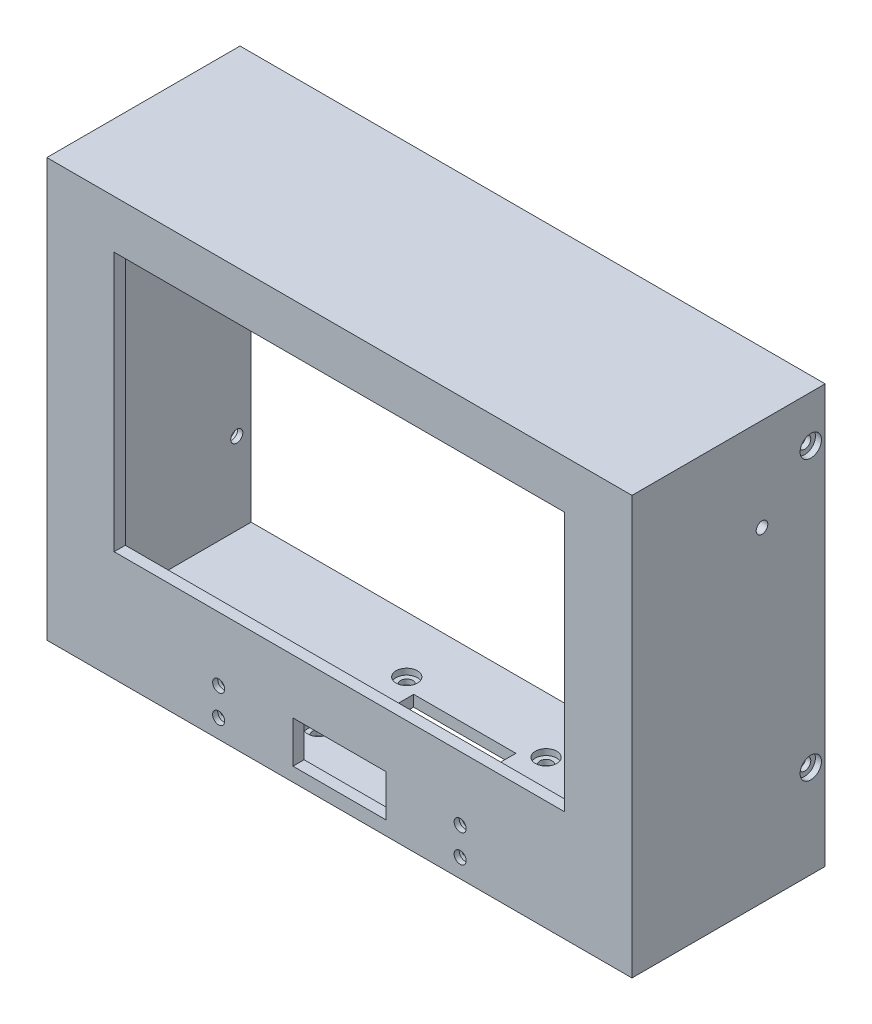
SolidWorks part; units mm, degrees
ref_plane "Front Plane" through (0, 0, 0) normal (0, 0, 1) x (1, 0, 0)
ref_plane "Top Plane" through (0, 0, 0) normal (0, 1, 0) x (1, 0, 0)
ref_plane "Right Plane" through (0, 0, 0) normal (1, 0, 0) x (0, 0, -1)
sketch "Sketch1" plane through (0, 0, 0) normal (0, 0, 1) x (1, 0, 0)
  line L1 (-63, 60) -> (63, 60)
  line L2 (-63, 60) -> (-63, 150)
  line L3 (-63, 150) -> (63, 150)
  line L4 (63, 60) -> (63, 150)
extrude "Boss-Extrude1" add sketch "Sketch1" along normal blind 41.6 from offset 38.4
sketch "Sketch2" plane through (0, 0, 0) normal (0, 0, 1) x (1, 0, 0)
  line L1 (-60.6, 62.4) -> (60.6, 62.4)
  line L2 (-60.6, 62.4) -> (-60.6, 147.6)
  line L3 (-60.6, 147.6) -> (60.6, 147.6)
  line L4 (60.6, 62.4) -> (60.6, 147.6)
extrude "Boss-Extrude2" add sketch "Sketch2" along normal blind 41.6 from offset 36 separate body
combine bodies "Combine1" operation type subtract main body 101 bodies to subtract 102
sketch "Sketch3" plane through (0, 0, 0) normal (0, 0, 1) x (1, 0, 0)
  line L1 (-48.5, 83.74) -> (48.5, 83.74)
  line L2 (-48.5, 83.74) -> (-48.5, 139.6)
  line L3 (-48.5, 139.6) -> (48.5, 139.6)
  line L4 (48.5, 83.74) -> (48.5, 139.6)
extrude "Boss-Extrude3" add sketch "Sketch3" along normal blind 4.4 from offset 76.6 separate body
combine bodies "Combine2" operation type subtract main body 103 bodies to subtract 104
sketch "Sketch4" plane through (0, 0, 0) normal (0, 0, 1) x (1, 0, 0)
  circle A0 centre (-56.3, 78.45) radius 2.8
extrude "Boss-Extrude4" add sketch "Sketch4" along normal blind 4.5 from offset 73.1
sketch "Sketch5" plane through (0, 0, 0) normal (0, 0, 1) x (1, 0, 0)
  circle A0 centre (-56.3, 78.45) radius 1
extrude "Boss-Extrude5" add sketch "Sketch5" along normal blind 7.1 from offset 72.1 separate body
combine bodies "Combine3" operation type subtract main body 106 bodies to subtract 107
sketch "Sketch6" plane through (0, 0, 0) normal (0, 0, 1) x (1, 0, 0)
  circle A0 centre (-56.3, 140.55) radius 2.8
extrude "Boss-Extrude6" add sketch "Sketch6" along normal blind 4.5 from offset 73.1
sketch "Sketch7" plane through (0, 0, 0) normal (0, 0, 1) x (1, 0, 0)
  circle A0 centre (-56.3, 140.55) radius 1
extrude "Boss-Extrude7" add sketch "Sketch7" along normal blind 7.1 from offset 72.1 separate body
combine bodies "Combine4" operation type subtract main body 109 bodies to subtract 110
sketch "Sketch8" plane through (0, 0, 0) normal (0, 0, 1) x (1, 0, 0)
  circle A0 centre (56.3, 78.45) radius 2.8
extrude "Boss-Extrude8" add sketch "Sketch8" along normal blind 4.5 from offset 73.1
sketch "Sketch9" plane through (0, 0, 0) normal (0, 0, 1) x (1, 0, 0)
  circle A0 centre (56.3, 78.45) radius 1
extrude "Boss-Extrude9" add sketch "Sketch9" along normal blind 7.1 from offset 72.1 separate body
combine bodies "Combine5" operation type subtract main body 112 bodies to subtract 113
sketch "Sketch10" plane through (0, 0, 0) normal (0, 0, 1) x (1, 0, 0)
  circle A0 centre (56.3, 140.55) radius 2.8
extrude "Boss-Extrude10" add sketch "Sketch10" along normal blind 4.5 from offset 73.1
sketch "Sketch11" plane through (0, 0, 0) normal (0, 0, 1) x (1, 0, 0)
  circle A0 centre (56.3, 140.55) radius 1
extrude "Boss-Extrude11" add sketch "Sketch11" along normal blind 7.1 from offset 72.1 separate body
combine bodies "Combine6" operation type subtract main body 115 bodies to subtract 116
sketch "Sketch12" plane through (0, 0, 0) normal (0, 0, 1) x (1, 0, 0)
  line L1 (-64, 107.5) -> (-60.1, 107.5)
  line L2 (-64, 107.5) -> (-64, 121.5)
  line L3 (-64, 121.5) -> (-60.1, 121.5)
  line L4 (-60.1, 107.5) -> (-60.1, 121.5)
extrude "Boss-Extrude12" add sketch "Sketch12" along normal blind 8 from offset 65.9 separate body
combine bodies "Combine7" operation type subtract main body 117 bodies to subtract 118
sketch "Sketch13" plane through (0, 0, 0) normal (1, 0, 0) x (0, 0, -1)
  circle A0 centre (-52, 130) radius 8.3
extrude "Boss-Extrude13" add sketch "Sketch13" along normal blind 1.2 from offset 60.6 offset against normal yes
sketch "Sketch14" plane through (0, 0, 0) normal (1, 0, 0) x (0, 0, -1)
  circle A0 centre (-52, 130) radius 7.3
extrude "Boss-Extrude14" add sketch "Sketch14" along normal blind 1.3 from offset 60.6 separate body offset against normal yes
combine bodies "Combine8" operation type subtract main body 120 bodies to subtract 121
sketch "Sketch15" plane through (0, 0, 0) normal (1, 0, 0) x (0, 0, -1)
  circle A0 centre (-52, 130) radius 1.25
extrude "Boss-Extrude15" add sketch "Sketch15" along normal blind 4.4 from offset 64 separate body offset against normal yes
combine bodies "Combine9" operation type subtract main body 122 bodies to subtract 123
sketch "Sketch16" plane through (0, 0, 0) normal (1, 0, 0) x (0, 0, -1)
  circle A0 centre (-41.5, 80) radius 1.3
extrude "Boss-Extrude16" add sketch "Sketch16" along normal blind 4.4 from offset 64 separate body offset against normal yes
combine bodies "Combine10" operation type subtract main body 124 bodies to subtract 125
sketch "Sketch17" plane through (0, 0, 0) normal (1, 0, 0) x (0, 0, -1)
  circle A0 centre (-41.5, 80) radius 2.3
extrude "Boss-Extrude17" add sketch "Sketch17" along normal blind 2.3 from offset 64 separate body offset against normal yes
combine bodies "Combine11" operation type subtract main body 126 bodies to subtract 127
sketch "Sketch18" plane through (0, 0, 0) normal (1, 0, 0) x (0, 0, -1)
  circle A0 centre (-41.5, 140) radius 1.3
extrude "Boss-Extrude18" add sketch "Sketch18" along normal blind 4.4 from offset 64 separate body offset against normal yes
combine bodies "Combine12" operation type subtract main body 128 bodies to subtract 129
sketch "Sketch19" plane through (0, 0, 0) normal (1, 0, 0) x (0, 0, -1)
  circle A0 centre (-41.5, 140) radius 2.3
extrude "Boss-Extrude19" add sketch "Sketch19" along normal blind 2.3 from offset 64 separate body offset against normal yes
combine bodies "Combine13" operation type subtract main body 130 bodies to subtract 131
sketch "Sketch20" plane through (0, 0, 0) normal (1, 0, 0) x (0, 0, -1)
  circle A0 centre (-52, 130) radius 8.3
extrude "Boss-Extrude20" add sketch "Sketch20" along normal blind 1.2 from offset 59.4
sketch "Sketch21" plane through (0, 0, 0) normal (1, 0, 0) x (0, 0, -1)
  circle A0 centre (-52, 130) radius 7.3
extrude "Boss-Extrude21" add sketch "Sketch21" along normal blind 1.3 from offset 59.3 separate body
combine bodies "Combine14" operation type subtract main body 133 bodies to subtract 134
sketch "Sketch22" plane through (0, 0, 0) normal (1, 0, 0) x (0, 0, -1)
  circle A0 centre (-52, 130) radius 1.25
extrude "Boss-Extrude22" add sketch "Sketch22" along normal blind 4.4 from offset 59.6 separate body
combine bodies "Combine15" operation type subtract main body 135 bodies to subtract 136
sketch "Sketch23" plane through (0, 0, 0) normal (1, 0, 0) x (0, 0, -1)
  circle A0 centre (-41.5, 80) radius 1.3
extrude "Boss-Extrude23" add sketch "Sketch23" along normal blind 4.4 from offset 59.6 separate body
combine bodies "Combine16" operation type subtract main body 137 bodies to subtract 138
sketch "Sketch24" plane through (0, 0, 0) normal (1, 0, 0) x (0, 0, -1)
  circle A0 centre (-41.5, 80) radius 2.3
extrude "Boss-Extrude24" add sketch "Sketch24" along normal blind 2.3 from offset 61.7 separate body
combine bodies "Combine17" operation type subtract main body 139 bodies to subtract 140
sketch "Sketch25" plane through (0, 0, 0) normal (1, 0, 0) x (0, 0, -1)
  circle A0 centre (-41.5, 140) radius 1.3
extrude "Boss-Extrude25" add sketch "Sketch25" along normal blind 4.4 from offset 59.6 separate body
combine bodies "Combine18" operation type subtract main body 141 bodies to subtract 142
sketch "Sketch26" plane through (0, 0, 0) normal (1, 0, 0) x (0, 0, -1)
  circle A0 centre (-41.5, 140) radius 2.3
extrude "Boss-Extrude26" add sketch "Sketch26" along normal blind 2.3 from offset 61.7 separate body
combine bodies "Combine19" operation type subtract main body 143 bodies to subtract 144
sketch "Sketch27" plane through (0, 0, 0) normal (0, 0, 1) x (1, 0, 0)
  line L1 (-11, 59) -> (11, 59)
  line L2 (-11, 59) -> (-11, 63.4)
  line L3 (-11, 63.4) -> (11, 63.4)
  line L4 (11, 59) -> (11, 63.4)
extrude "Boss-Extrude27" add sketch "Sketch27" along normal blind 14 from offset 53 separate body
combine bodies "Combine20" operation type subtract main body 145 bodies to subtract 146
sketch "Sketch28" plane through (0, 0, 0) normal (0, 1, 0) x (1, 0, 0)
  circle A0 centre (-15, -50.5) radius 1.3
extrude "Boss-Extrude28" add sketch "Sketch28" along normal blind 4.4 from offset 59 separate body
combine bodies "Combine21" operation type subtract main body 147 bodies to subtract 148
sketch "Sketch29" plane through (0, 0, 0) normal (0, 1, 0) x (1, 0, 0)
  circle A0 centre (-15, -50.5) radius 2.3
extrude "Boss-Extrude29" add sketch "Sketch29" along normal blind 1.8 from offset 61.1 separate body
combine bodies "Combine22" operation type subtract main body 149 bodies to subtract 150
sketch "Sketch30" plane through (0, 0, 0) normal (0, 1, 0) x (1, 0, 0)
  circle A0 centre (-15, -69.5) radius 1.3
extrude "Boss-Extrude30" add sketch "Sketch30" along normal blind 4.4 from offset 59 separate body
combine bodies "Combine23" operation type subtract main body 151 bodies to subtract 152
sketch "Sketch31" plane through (0, 0, 0) normal (0, 1, 0) x (1, 0, 0)
  circle A0 centre (-15, -69.5) radius 2.3
extrude "Boss-Extrude31" add sketch "Sketch31" along normal blind 1.8 from offset 61.1 separate body
combine bodies "Combine24" operation type subtract main body 153 bodies to subtract 154
sketch "Sketch32" plane through (0, 0, 0) normal (0, 1, 0) x (1, 0, 0)
  circle A0 centre (15, -50.5) radius 1.3
extrude "Boss-Extrude32" add sketch "Sketch32" along normal blind 4.4 from offset 59 separate body
combine bodies "Combine25" operation type subtract main body 155 bodies to subtract 156
sketch "Sketch33" plane through (0, 0, 0) normal (0, 1, 0) x (1, 0, 0)
  circle A0 centre (15, -50.5) radius 2.3
extrude "Boss-Extrude33" add sketch "Sketch33" along normal blind 1.8 from offset 61.1 separate body
combine bodies "Combine26" operation type subtract main body 157 bodies to subtract 158
sketch "Sketch34" plane through (0, 0, 0) normal (0, 1, 0) x (1, 0, 0)
  circle A0 centre (15, -69.5) radius 1.3
extrude "Boss-Extrude34" add sketch "Sketch34" along normal blind 4.4 from offset 59 separate body
combine bodies "Combine27" operation type subtract main body 159 bodies to subtract 160
sketch "Sketch35" plane through (0, 0, 0) normal (0, 1, 0) x (1, 0, 0)
  circle A0 centre (15, -69.5) radius 2.3
extrude "Boss-Extrude35" add sketch "Sketch35" along normal blind 1.8 from offset 61.1 separate body
combine bodies "Combine28" operation type subtract main body 161 bodies to subtract 162
sketch "Sketch36" plane through (0, 0, 0) normal (0, 0, 1) x (1, 0, 0)
  line L1 (-10, 63) -> (10, 63)
  line L2 (-10, 63) -> (-10, 72)
  line L3 (-10, 72) -> (10, 72)
  line L4 (10, 63) -> (10, 72)
extrude "Boss-Extrude36" add sketch "Sketch36" along normal blind 4.4 from offset 76.6 separate body
combine bodies "Combine29" operation type subtract main body 163 bodies to subtract 164
sketch "Sketch37" plane through (0, 0, 0) normal (0, 0, 1) x (1, 0, 0)
  circle A0 centre (-26, 64) radius 1.3
extrude "Boss-Extrude37" add sketch "Sketch37" along normal blind 4.4 from offset 76.6 separate body
combine bodies "Combine30" operation type subtract main body 165 bodies to subtract 166
sketch "Sketch38" plane through (0, 0, 0) normal (0, 0, 1) x (1, 0, 0)
  circle A0 centre (-26, 64) radius 2.3
extrude "Boss-Extrude38" add sketch "Sketch38" along normal blind 1.8 from offset 77.1 separate body
combine bodies "Combine31" operation type subtract main body 167 bodies to subtract 168
sketch "Sketch39" plane through (0, 0, 0) normal (0, 0, 1) x (1, 0, 0)
  circle A0 centre (-26, 70) radius 1.3
extrude "Boss-Extrude39" add sketch "Sketch39" along normal blind 4.4 from offset 76.6 separate body
combine bodies "Combine32" operation type subtract main body 169 bodies to subtract 170
sketch "Sketch40" plane through (0, 0, 0) normal (0, 0, 1) x (1, 0, 0)
  circle A0 centre (-26, 70) radius 2.3
extrude "Boss-Extrude40" add sketch "Sketch40" along normal blind 1.8 from offset 77.1 separate body
combine bodies "Combine33" operation type subtract main body 171 bodies to subtract 172
sketch "Sketch41" plane through (0, 0, 0) normal (0, 0, 1) x (1, 0, 0)
  circle A0 centre (26, 64) radius 1.3
extrude "Boss-Extrude41" add sketch "Sketch41" along normal blind 4.4 from offset 76.6 separate body
combine bodies "Combine34" operation type subtract main body 173 bodies to subtract 174
sketch "Sketch42" plane through (0, 0, 0) normal (0, 0, 1) x (1, 0, 0)
  circle A0 centre (26, 64) radius 2.3
extrude "Boss-Extrude42" add sketch "Sketch42" along normal blind 1.8 from offset 77.1 separate body
combine bodies "Combine35" operation type subtract main body 175 bodies to subtract 176
sketch "Sketch43" plane through (0, 0, 0) normal (0, 0, 1) x (1, 0, 0)
  circle A0 centre (26, 70) radius 1.3
extrude "Boss-Extrude43" add sketch "Sketch43" along normal blind 4.4 from offset 76.6 separate body
combine bodies "Combine36" operation type subtract main body 177 bodies to subtract 178
sketch "Sketch44" plane through (0, 0, 0) normal (0, 0, 1) x (1, 0, 0)
  circle A0 centre (26, 70) radius 2.3
extrude "Boss-Extrude44" add sketch "Sketch44" along normal blind 1.8 from offset 77.1 separate body
combine bodies "Combine37" operation type subtract main body 179 bodies to subtract 180
